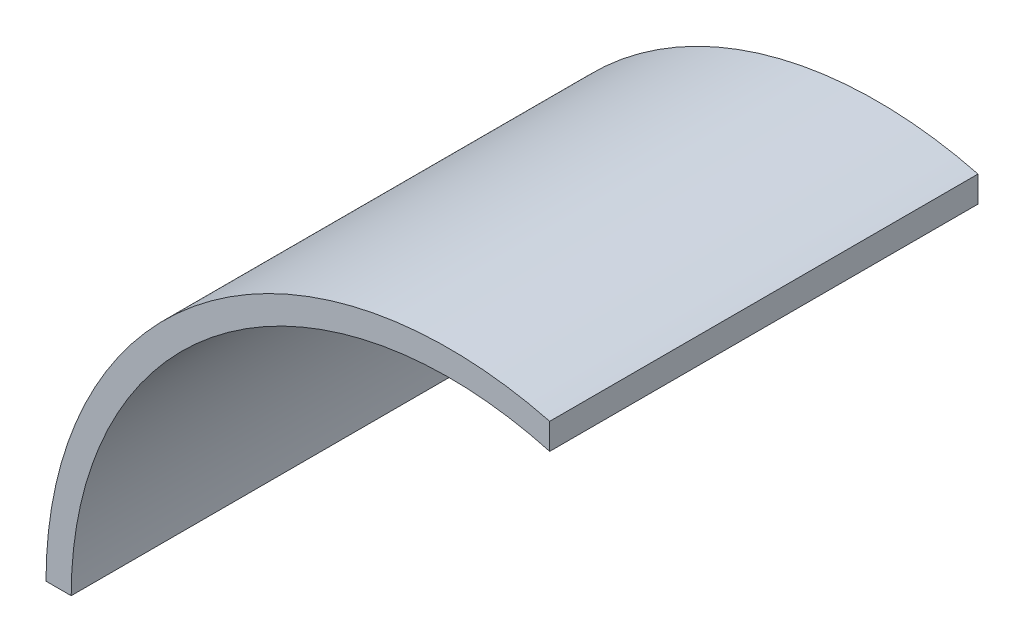
SolidWorks part; units mm, degrees
material "201 Annealed Stainless Steel (SS)"
ref_plane "Front Plane" through (0, 0, 0) normal (0, 0, 1) x (1, 0, 0)
ref_plane "Top Plane" through (0, 0, 0) normal (0, 1, 0) x (1, 0, 0)
ref_plane "Right Plane" through (0, 0, 0) normal (1, 0, 0) x (0, 0, -1)
sketch "Sketch1" plane through (0, 0, 0) normal (0, 0, 1) x (1, 0, 0)
  line L0 (0, 0) -> (0, -160) construction
  line L2 (0, 0) -> (101.5936, 0) construction
  line L3 (39.9343, 113.7839) -> (39.9343, -22.985) construction
  line L5 (39.9343, 154.9363) -> (39.9343, 144.5865)
  line L7 (0, 0) -> (-150, 0) construction
  line L25 (-160, 0) -> (-150, 0)
  circle A0 centre (0, 0) radius 150 construction
  circle A1 centre (0, 0) radius 160 construction
  arc A2 (-150, 0) -> (39.9343, 144.5865) centre (0, 0) cw
  arc A3 (-160, 0) -> (39.9343, 154.9363) centre (0, 0) cw
  point P4 (0, 0)
  point P6 (0, 0)
  point P10 (39.9343, 144.5865)
  point P14 (0, 0)
  dimension "D1" = 300
  dimension "D2" = 320
  dimension "D3" = 39.9343
extrude "Inner Ring - Left Side" add sketch "Sketch1" along normal blind 170
